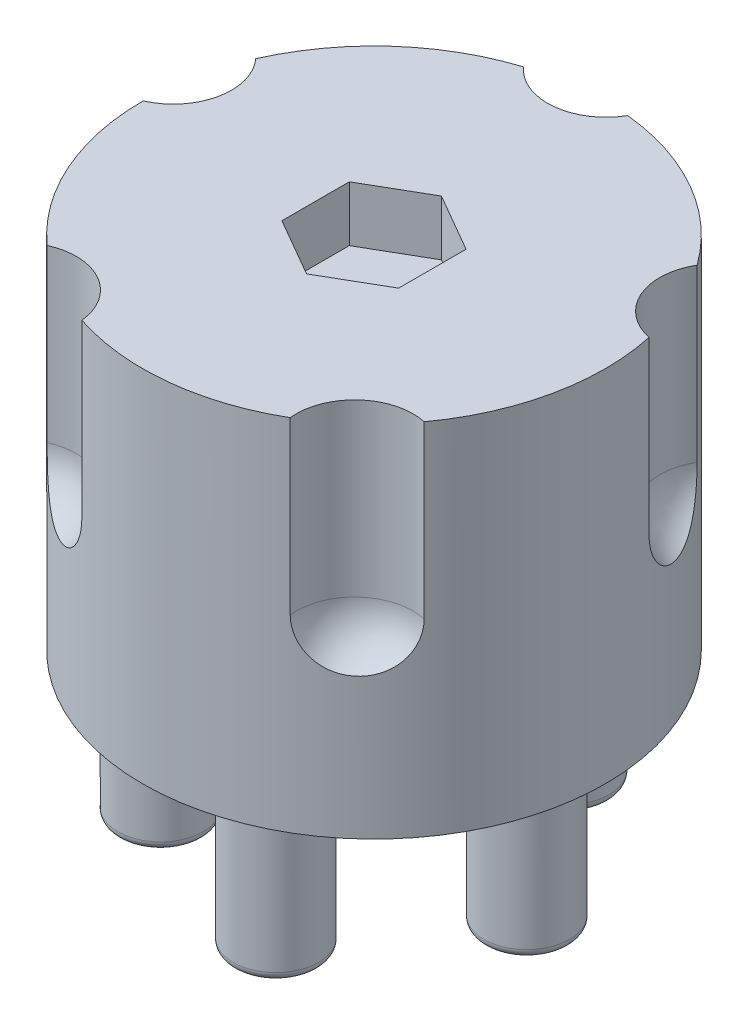
SolidWorks part; units mm, degrees
ref_plane "Front Plane" through (0, 0, 0) normal (0, 0, 1) x (1, 0, 0)
ref_plane "Top Plane" through (0, 0, 0) normal (0, 1, 0) x (1, 0, 0)
ref_plane "Right Plane" through (0, 0, 0) normal (1, 0, 0) x (0, 0, -1)
sketch "Sketch1" plane through (0, 0, 0) normal (0, 1, 0) x (1, 0, 0)
  circle A0 centre (0, 0) radius 25.75
  dimension "D1" = 51.5
extrude "Boss-Extrude1" add sketch "Sketch1" along normal blind 40
sketch "Sketch2" plane through (0, 0, 0) normal (0, -1, 0) x (1, 0, 0)
  circle A0 centre (0, 0) radius 17 construction
  circle A1 centre (17, 0) radius 4.75
  circle A2 centre (5.2533, -16.168) radius 4.75
  circle A3 centre (-13.7533, -9.9923) radius 4.75
  circle A4 centre (-13.7533, 9.9923) radius 4.75
  circle A5 centre (5.2533, 16.168) radius 4.75
  point P5 (7.9036, -19.623)
  point P6 (0, 0)
  point P7 (5.03, -15.4807)
  point P16 (0, 0)
  dimension "D2" = 9.5
  dimension "D3" = 34
  dimension "D1" = 5
extrude "Boss-Extrude2" add sketch "Sketch2" along normal blind 18
fillet "Fillet1" radius 1 5 edges at (5.2533, 0, 20.918) (-13.7533, 0, 14.7423) (-13.7533, 0, -5.2423) (5.2533, 0, -11.418) (17, 0, 4.75)
fillet "Fillet2" radius 1 5 edges at (-13.7533, -18, -14.7423) (-13.7533, -18, 5.2423) (5.2533, -18, 11.418) (17, -18, -4.75) (5.2533, -18, -20.918)
sketch "Sketch3" plane through (0, 40, 0) normal (0, 1, 0) x (1, 0, 0)
  line L1 (0, -7.5) -> (6.4952, -3.75)
  line L2 (6.4952, -3.75) -> (6.4952, 3.75)
  line L3 (6.4952, 3.75) -> (0, 7.5)
  line L4 (0, 7.5) -> (-6.4952, 3.75)
  line L5 (-6.4952, 3.75) -> (-6.4952, -3.75)
  line L6 (-6.4952, -3.75) -> (0, -7.5)
  circle A0 centre (0, 0) radius 6.4952 construction
  point P1 (6.6275, -3.5108)
  dimension "D1" = 15
extrude "Cut-Extrude1" cut sketch "Sketch3" against normal blind 6.15
sketch "Sketch4" plane through (0, 0, 0) normal (0, -1, 0) x (1, 0, 0)
  circle A0 centre (0, 0) radius 10
  dimension "D1" = 20
extrude "Cut-Extrude2" cut sketch "Sketch4" against normal blind 22
sketch "Sketch5" plane through (0, 22, 0) normal (0, -1, 0) x (1, 0, 0)
  circle A0 centre (0, 0) radius 4
  dimension "D1" = 8
extrude "Cut-Extrude3" cut sketch "Sketch5" against normal blind 11.5
chamfer "Chamfer2" distance 5 distance2 5 1 edges at (0, 22, -4)
sketch "Sketch6" plane through (0, 40, 0) normal (0, 1, 0) x (1, 0, 0)
  line L0 (-3.2476, -5.625) -> (-14.5, -25.1147) construction
  line L1 (-6.4952, -3.75) -> (0, -7.5) construction
  circle A0 centre (0, 0) radius 29 construction
  circle A1 centre (-14.5, -25.1147) radius 6.5
  circle A2 centre (-28.3663, 6.0294) radius 6.5
  circle A3 centre (-3.0313, 28.8411) radius 6.5
  circle A4 centre (26.4928, 11.7954) radius 6.5
  circle A5 centre (19.4048, -21.5512) radius 6.5
  point P3 (-27.741, 5.8965)
  point P5 (0, 0)
  point P16 (0, 0)
  point P19 (-18.9509, -32.8239)
  point P20 (-17.2809, -31.1436)
  dimension "D2" = 13
  dimension "D3" = 58
  dimension "D1" = 5
extrude "Cut-Extrude4" cut sketch "Sketch6" against normal blind 25
fillet "Fillet3" radius 6 5 edges at (-11.25, 15, 19.4856) (20.5548, 15, -9.1516) (-2.3519, 15, -22.3767) (-22.0083, 15, -4.678) (15.0554, 15, 16.7208)
